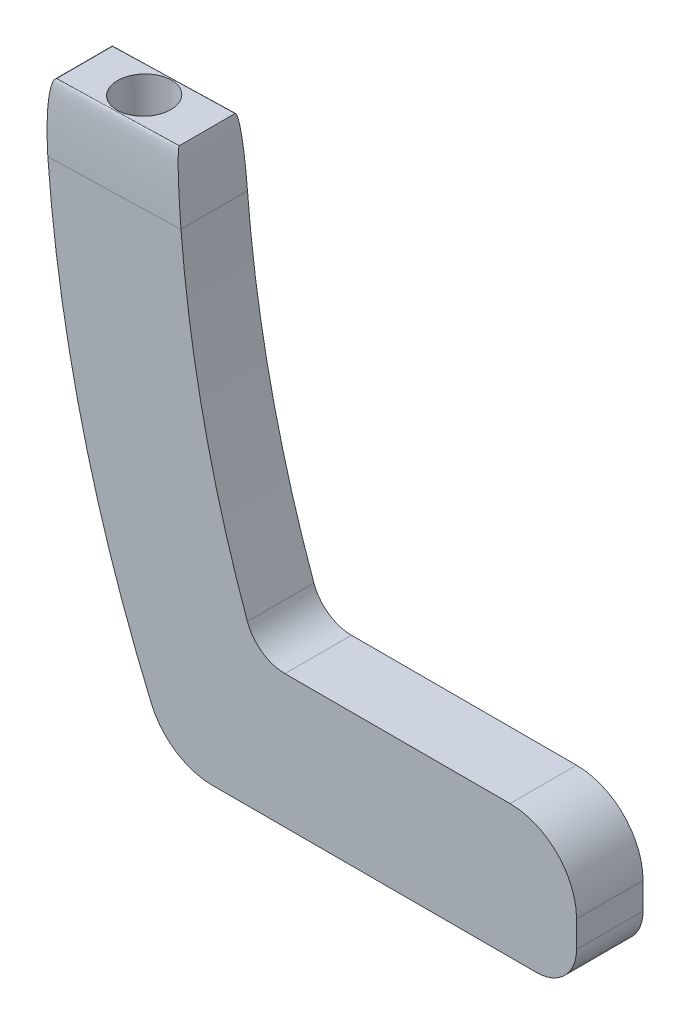
SolidWorks part; units mm, degrees
ref_plane "Front Plane" through (0, 0, 0) normal (0, 0, 1) x (1, 0, 0)
ref_plane "Top Plane" through (0, 0, 0) normal (0, 1, 0) x (1, 0, 0)
ref_plane "Right Plane" through (0, 0, 0) normal (1, 0, 0) x (0, 0, -1)
sketch "Sketch1" plane through (0, 0, 0) normal (0, 0, 1) x (1, 0, 0)
  line L0 (0, 0) -> (0, -30) construction
  line L1 (0, -30) -> (6, -30) construction
  line L2 (6, -30) -> (30, -30)
  arc A0 (0, 0) -> (6, -30) centre (89.5281, 2.3056) ccw
extrude "Extrude-Thin1" add sketch "Sketch1" along normal blind 5 thin thin type one direction wall 10
sketch "Sketch2" plane through (0, 0, 0) normal (0, 1, 0) x (1, 0, 0)
  line L0 (-9.9967, -2.5) -> (0, -2.5) construction
  line L1 (-9.9967, -5) -> (-9.9967, 0) construction
  line L2 (0, -5) -> (0, 0) construction
  line L3 (-4.9983, 0) -> (-4.9983, -5) construction
  line L4 (-9.9967, 0) -> (0, 0) construction
  line L5 (-9.9967, -5) -> (0, -5) construction
  circle A0 centre (-4.9983, -2.5) radius 2
extrude "Cut-Extrude1" cut sketch "Sketch2" against normal blind 3
fillet "Fillet1" radius 5 1 edges at (30, -30, 2.5)
fillet "Fillet2" radius 3 1 edges at (30, -40, 2.5)
fillet "Fillet3" radius 3 1 edges at (6, -30, 2.5)
fillet "Fillet4" radius 5 4 edges at (-4.9983, -0.1287, 0) (-9.9967, -0.2574, 2.5) (-4.9983, -0.1287, 5) (0, 0, 2.5) second distance 0.4 first distance on face at (12.5458, -26.7781, 0) first distance on face at (-6.3252, -20.3724, 2.5) first distance on face at (12.5458, -26.7781, 5) first distance on face at (2.0688, -14.1131, 2.5)
fillet "Fillet5" radius 5 1 edges at (-0.594, -40, 2.5)
